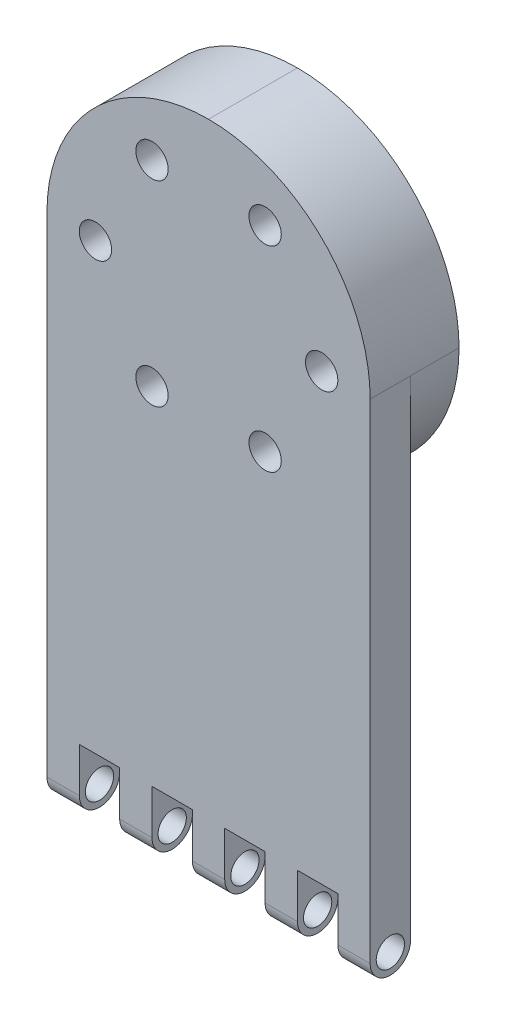
SolidWorks part; units mm, degrees
other "Markup1"
sketch "Sketch13" plane through (20, -53, 11) normal (0.0614, -0.6805, 0.7302) x (0.9699, -0.1321, -0.2046)
ref_plane "Front Plane" through (0, 0, 0) normal (0, 0, 1) x (1, 0, 0)
ref_plane "Top Plane" through (0, 0, 0) normal (0, 1, 0) x (1, 0, 0)
ref_plane "Right Plane" through (0, 0, 0) normal (1, 0, 0) x (0, 0, -1)
sketch "Sketch7" plane through (0, 0, 0) normal (0, 0, 1) x (1, 0, 0)
  line L1 (-20, 20) -> (20, 20)
  line L2 (-20, 20) -> (-20, -20)
  line L3 (-20, -20) -> (20, -20)
  line L4 (20, 20) -> (20, -20)
  line L5 (-20, 20) -> (20, -20) construction
  line L6 (-20, -20) -> (20, 20) construction
  point P0 (0, 0)
extrude "Boss-Extrude1" add sketch "Sketch7" along normal blind 11
sketch "Sketch8" plane through (0, -20, 0) normal (0, -1, 0) x (1, 0, 0)
  line L0 (20, 11) -> (20, 0) construction
  line L1 (-20, 11) -> (20, 11)
  line L2 (-20, 11) -> (-20, 6)
  line L3 (-20, 6) -> (20, 6)
  line L4 (20, 11) -> (20, 6)
  line L5 (0, 6) -> (0, 11) construction
  line L6 (-20, 8.5) -> (20, 8.5) construction
  point P764 (0, 8.5)
extrude "Boss-Extrude2" add sketch "Sketch8" along normal blind 35
sketch "Sketch10" plane through (0, 0, 11) normal (0, 0, 1) x (1, 0, 0)
  circle A0 centre (-7.0001, 12.1244) radius 2
  circle A1 centre (6.9999, 12.1244) radius 2
  circle A2 centre (13.9999, 0.0001) radius 2
  circle A3 centre (6.9999, -12.1243) radius 2
  circle A4 centre (-7.0001, -12.1243) radius 2
  circle A5 centre (-14.0001, 0.0001) radius 2
  point P0 (0, 0)
  point P1 (0.0025, 0.0011)
  dimension "D1" = 4
  dimension "D2" = 4
  dimension "D3" = 4
  dimension "D4" = 4
  dimension "D5" = 4
  dimension "D6" = 4
extrude "Cut-Extrude1" cut sketch "Sketch10" against normal blind 25
fillet "Fillet1" radius 20 4 edges at (20, -20, 3) (20, 20, 5.5) (-20, 20, 5.5) (-20, -20, 3)
sketch "Sketch11" plane through (0, -55, 0) normal (0, -1, 0) x (1, 0, 0)
  line L0 (-20, 6) -> (20, 6) construction
  line L1 (-20, 11) -> (-16, 11)
  line L2 (-20, 11) -> (-20, 6)
  line L3 (-20, 6) -> (-16, 6)
  line L4 (-16, 11) -> (-16, 6)
  line L5 (-18, 6) -> (-18, 11) construction
  line L6 (-20, 8.5) -> (-16, 8.5) construction
  point P368 (-18, 8.5)
extrude "Boss-Extrude3" add sketch "Sketch11" along normal blind 8 contours L1 L4 L3 L2
fillet "Fillet2" radius 2.5 2 edges at (-18, -63, 6) (-18, -63, 11)
pattern_linear "LPattern1" count 5 spacing 9 along (1, 0, 0) of "Fillet2", "Boss-Extrude3"
sketch "Sketch12" plane through (20, 0, 0) normal (1, 0, 0) x (0, 0, -1)
  circle A0 centre (-8.5, -60.5) radius 1.75
extrude "Cut-Extrude2" cut sketch "Sketch12" against normal through all both and the other way through all
